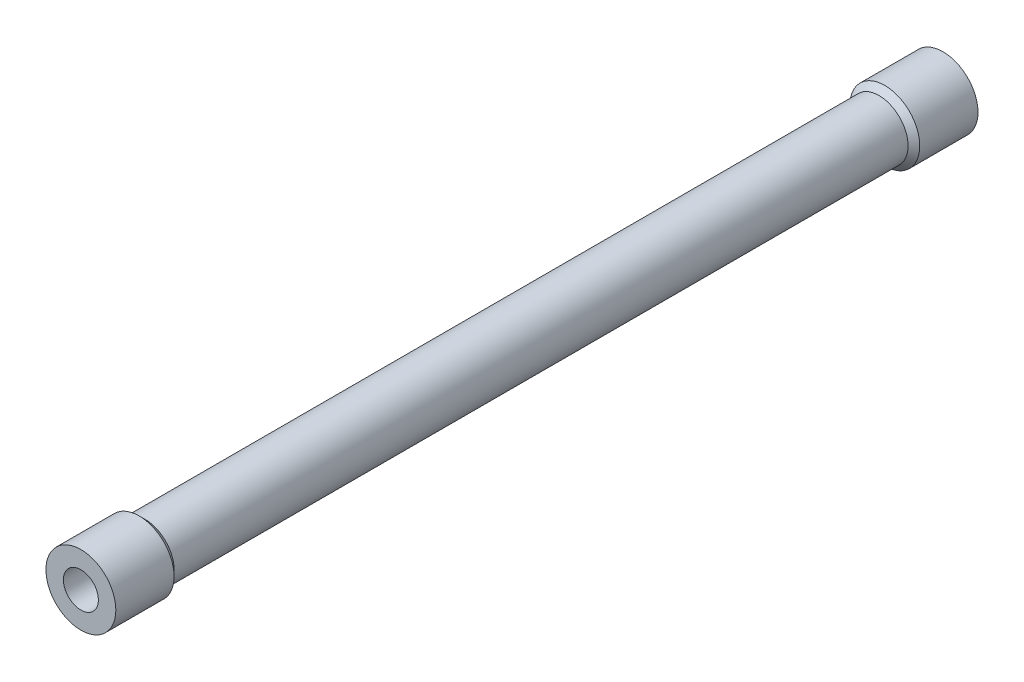
SolidWorks part; units mm, degrees
material "1060 Alloy"
ref_plane "Front Plane" through (0, 0, 0) normal (0, 0, 1) x (1, 0, 0)
ref_plane "Top Plane" through (0, 0, 0) normal (0, 1, 0) x (1, 0, 0)
ref_plane "Right Plane" through (0, 0, 0) normal (1, 0, 0) x (0, 0, -1)
sketch "Sketch1" plane through (0, 0, 0) normal (0, 0, 1) x (1, 0, 0)
  circle A0 centre (0, 0) radius 2.5
  circle A1 centre (0, 0) radius 1.5
  dimension "D1" = 5
  dimension "D2" = 3
extrude "Boss-Extrude1" add sketch "Sketch1" along normal blind 74
sketch "Sketch2" plane through (0, 0, 74) normal (0, 0, 1) x (1, 0, 0)
  circle A2 centre (0, 0) radius 1.5
  circle A3 centre (0, 0) radius 1.5
  circle A5 centre (0, 0) radius 3
  circle A6 centre (0, 0) radius 3
  dimension "D1" = 0
  dimension "D2" = 0.5
extrude "Boss-Extrude2" add sketch "Sketch2" against normal blind 6
chamfer "Chamfer1" distance 1 angle 45 1 edges at (3, 0, 68)
ref_plane "Plane1" through (0, 0, 37) normal (0, 0, 1) x (1, 0, 0)
mirror "Mirror1" about plane through (0, 0, 37) normal (0, 0, 1) of "Boss-Extrude2", "Chamfer1"
